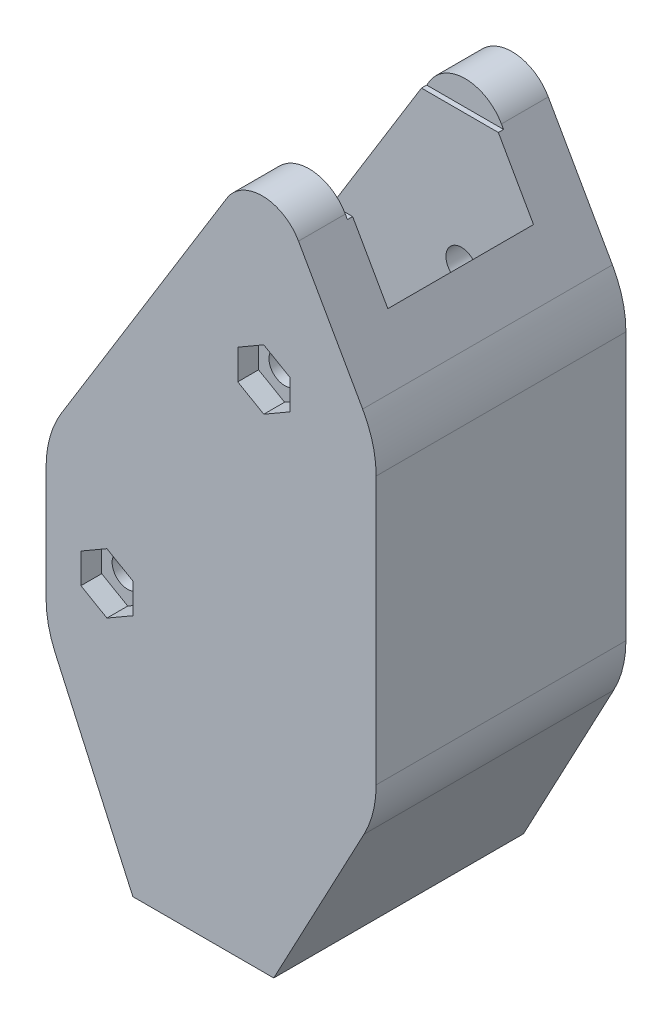
SolidWorks part; units mm, degrees
ref_plane "前视基准面" through (0, 0, 0) normal (0, 0, 1) x (1, 0, 0)
ref_plane "上视基准面" through (0, 0, 0) normal (0, 1, 0) x (1, 0, 0)
ref_plane "右视基准面" through (0, 0, 0) normal (1, 0, 0) x (0, 0, -1)
sketch "草图1" plane through (0, 0, 0) normal (0, 0, 1) x (1, 0, 0)
  line L8 (-29.8155, -4.2167) -> (49970.1845, -4.2167) construction
  line L9 (-29.8155, -28.7167) -> (49970.1845, -28.7167) construction
  line L10 (-8.8963, -4.2167) -> (26190.399, -42590.5634) construction
  line L20 (-8.8963, -35.0463) -> (-8.8963, 49964.9537) construction
  line L21 (-29.8155, -35.0463) -> (12.023, -35.0463)
  line L22 (-29.8155, -35.0463) -> (-29.8155, 26.613)
  line L23 (-29.8155, 26.613) -> (12.023, 26.613)
  line L24 (12.023, -35.0463) -> (12.023, 26.613)
  circle A0 centre (-8.8963, -4.2167) radius 1.5
  circle A1 centre (6.1762, -28.7167) radius 1.5
  point P5 (-29.8155, -4.2167)
  point P9 (-8.8963, -35.0463)
  dimension "D1" = 24.5
  dimension "D2" = 3
  dimension "D6" = 121.6
  dimension "D3" = 20.9193
  dimension "D7" = 3
  dimension "D4" = 61.6593
  dimension "D5" = 41.8385
extrude "凸台-拉伸1" add sketch "草图1" along normal blind 24
shell "抽壳2" thickness 5 removed face at (-8.8963, -35.0463, 12) removed face at (12.023, -4.2167, 12) removed face at (-8.8963, 26.613, 12)
sketch "草图7" plane through (12.023, 0, 0) normal (1, 0, 0) x (0, 0, -1)
  line L1 (-19, 26.613) -> (-5, 26.613)
  line L2 (-19, 26.613) -> (-19, -35.0463)
  line L3 (-19, -35.0463) -> (-5, -35.0463)
  line L4 (-5, 26.613) -> (-5, -35.0463)
  dimension "D1" = 61.6593
  dimension "D2" = 14
extrude "切除-拉伸2" cut sketch "草图7" against normal blind 38
sketch "草图11" plane through (-29.8155, 0, 0) normal (-1, 0, 0) x (0, 0, 1)
  line L1 (19, 26.613) -> (5, 26.613)
  line L2 (19, 26.613) -> (19, -35.0463)
  line L3 (19, -35.0463) -> (5, -35.0463)
  line L4 (5, 26.613) -> (5, -35.0463)
  dimension "D1" = 61.6593
  dimension "D2" = 14
extrude "凸台-拉伸2" add sketch "草图11" against normal blind 14
sketch "草图12" plane through (0, 0, 24) normal (0, 0, 1) x (1, 0, 0)
  line L1 (-29.8155, 26.613) -> (-19.6941, 26.613)
  line L2 (-29.8155, 26.613) -> (-29.8155, -35.0463)
  line L3 (-29.8155, -35.0463) -> (-19.6941, -35.0463)
  line L4 (-19.6941, 26.613) -> (-19.6941, -35.0463)
  line L5 (-29.8155, -35.0463) -> (12.023, -35.0463) construction
  dimension "D1" = 61.6593
  dimension "D2" = 10.1214
extrude "切除-拉伸3" cut sketch "草图12" against normal through all
sketch "草图17" plane through (0, 0, 24) normal (0, 0, 1) x (1, 0, 0)
  line L0 (-8.8963, -4.2167) -> (-8.8963, 49995.7833) construction
  line L1 (-8.8963, 26.613) -> (-8.8963, 14.8678)
  line L2 (12.023, 26.613) -> (-19.6941, 26.613) construction
  line L3 (-8.8963, 14.8678) -> (12.023, -19.136)
  line L4 (12.023, -35.0463) -> (12.023, 26.613) construction
  line L5 (12.023, -19.136) -> (12.023, 26.613)
  line L6 (12.023, 26.613) -> (-8.8963, 26.613)
  line L7 (-8.8963, -4.2167) -> (26190.399, -42590.5634) construction
  dimension "D1" = 10
extrude "切除-拉伸5" cut sketch "草图17" against normal through all
sketch "草图18" plane through (-19.6941, 0, 0) normal (-1, 0, 0) x (0, 0, 1)
  line L0 (0, 26.613) -> (24, 26.613) construction
  line L1 (4.5, 26.613) -> (19.5, 26.613)
  line L2 (4.5, 26.613) -> (4.5, 8.613)
  line L3 (4.5, 8.613) -> (19.5, 8.613)
  line L4 (19.5, 26.613) -> (19.5, 8.613)
  line L5 (0, -35.0463) -> (0, 26.613) construction
  line L6 (24, -35.0463) -> (24, 26.613) construction
  dimension "D1" = 18
  dimension "D2" = 15
  dimension "D3" = 4.5
  dimension "D4" = 4.5
extrude "切除-拉伸6" cut sketch "草图18" against normal through all
sketch "草图20" plane through (0, 0, 24) normal (0, 0, 1) x (1, 0, 0)
  line L0 (-19.6941, -35.0463) -> (-9.8535, -53.541)
  line L1 (-9.8535, -53.541) -> (3.6836, -53.541)
  line L2 (3.6836, -53.541) -> (12.023, -35.0463)
  line L3 (12.023, -35.0463) -> (-19.6941, -35.0463)
extrude "凸台-拉伸5" add sketch "草图20" against normal blind 24
sketch "草图22" plane through (0, -35.0463, 0) normal (0, 1, 0) x (1, 0, 0)
  line L1 (-15.8155, -5) -> (12.023, -5)
  line L2 (-15.8155, -5) -> (-15.8155, -19)
  line L3 (-15.8155, -19) -> (12.023, -19)
  line L4 (12.023, -5) -> (12.023, -19)
  dimension "D1" = 14
  dimension "D2" = 27.8385
extrude "切除-拉伸8" cut sketch "草图22" against normal blind 17
ref_plane "基准面4" through (-29.8818, -15.8995, 0) normal (0.8828, 0.4697, 0) x (0, 0, -1)
sketch "草图23" plane through (-29.8818, -15.8995, 0) normal (0.8828, 0.4697, 0) x (0, 0, -1)
  line L5 (-19.4003, -29.5799) -> (-4.4092, -29.5799)
  line L6 (-19.4003, -29.5799) -> (-19.4003, -41.3133)
  line L7 (-19.4003, -41.3133) -> (-4.4092, -41.3133)
  line L8 (-4.4092, -29.5799) -> (-4.4092, -41.3133)
  dimension "D1" = 11.7334
  dimension "D2" = 14.9912
extrude "凸台-拉伸8" add sketch "草图23" along normal blind 2
fillet "圆角3" radius 4 1 edges at (-14.2217, -41.0735, 12)
sketch "草图24" plane through (0, 0, 0) normal (0, 0, -1) x (-1, 0, 0)
  line L0 (8.8963, 14.8678) -> (19.6941, -4.2167)
  line L1 (19.6941, -35.0463) -> (19.6941, 26.613) construction
  line L2 (19.6941, -4.2167) -> (19.6941, 26.613)
  line L3 (19.6941, 26.613) -> (8.8963, 26.613)
  line L4 (8.8963, 26.613) -> (8.8963, 14.8678)
extrude "切除-拉伸9" cut sketch "草图24" against normal through all
fillet "圆角4" radius 4 2 edges at (-8.8963, 14.8678, 21.75) (-8.8963, 14.8678, 2.25)
fillet "圆角5" radius 10 6 edges at (-19.6941, -35.0463, 12) (-19.6941, -4.2167, 12) (12.023, -35.0463, 21.5) (12.023, -35.0463, 2.5) (12.023, -19.136, 2.5) (12.023, -19.136, 21.5)
sketch "草图25" plane through (0, 0, 24) normal (0, 0, 1) x (1, 0, 0)
  line L0 (-19.6941, -32.5515) -> (-19.6941, -6.8495) construction
  line L1 (-8.8963, -7.1034) -> (-6.3963, -5.6601)
  line L2 (-6.3963, -5.6601) -> (-6.3963, -2.7733)
  line L3 (-6.3963, -2.7733) -> (-8.8963, -1.3299)
  line L4 (-8.8963, -1.3299) -> (-11.3963, -2.7733)
  line L5 (-11.3963, -2.7733) -> (-11.3963, -5.6601)
  line L6 (-11.3963, -5.6601) -> (-8.8963, -7.1034)
  line L7 (6.1762, -25.8299) -> (3.6762, -27.2733)
  line L8 (3.6762, -27.2733) -> (3.6762, -30.1601)
  line L9 (3.6762, -30.1601) -> (6.1762, -31.6034)
  line L10 (6.1762, -31.6034) -> (8.6762, -30.1601)
  line L11 (8.6762, -30.1601) -> (8.6762, -27.2733)
  line L12 (8.6762, -27.2733) -> (6.1762, -25.8299)
  circle A0 centre (-8.8963, -4.2167) radius 2.5 construction
  circle A1 centre (6.1762, -28.7167) radius 2.5 construction
  dimension "D1" = 5
  dimension "D2" = 5
extrude "切除-拉伸10" cut sketch "草图25" against normal blind 2
sketch "草图26" plane through (0, 0, 0) normal (0, 0, -1) x (-1, 0, 0)
  circle A0 centre (8.8963, -4.2167) radius 2.5
  circle A1 centre (-6.1762, -28.7167) radius 2.5
  dimension "D1" = 5
  dimension "D2" = 5
extrude "切除-拉伸11" cut sketch "草图26" against normal blind 1
ref_plane "基准面5" through (-29.6941, 0, 0) normal (-1, 0, 0) x (0, 0, 1)
mirror "镜向1" about plane through (-29.6941, 0, 0) normal (-1, 0, 0) of bodies 123
delete or keep bodies "实体-删除/保留 1" type delete bodies bodies 123
